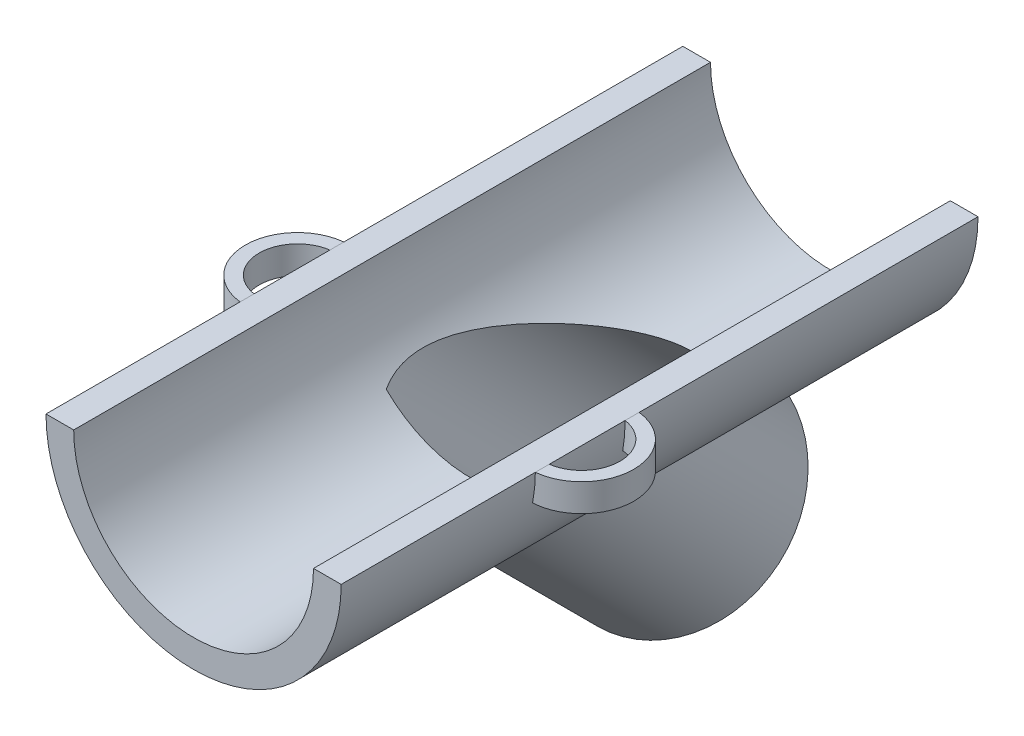
SolidWorks part; units mm, degrees
ref_plane "Front Plane" through (0, 0, 0) normal (0, 0, 1) x (1, 0, 0)
ref_plane "Top Plane" through (0, 0, 0) normal (0, 1, 0) x (1, 0, 0)
ref_plane "Right Plane" through (0, 0, 0) normal (1, 0, 0) x (0, 0, -1)
sketch "Sketch2" plane through (0, 0, 0) normal (0, 0, 1) x (1, 0, 0)
  line L0 (13.54, 0) -> (11, 0)
  line L1 (-11, 0) -> (-13.54, 0)
  arc A0 (-11, 0) -> (11, 0) centre (0, 0) ccw
  arc A1 (-13.54, 0) -> (13.54, 0) centre (0, 0) ccw
  dimension "D1" = 22
  dimension "D2" = 2.54
extrude "Boss-Extrude1" add sketch "Sketch2" along normal blind 76.2
ref_plane "Plane1" through (0, 0, 0) normal (0, 0.7071, 0.7071) x (-1, 0, 0)
sketch "Sketch4" plane through (0, 0, 0) normal (0, 0.7071, 0.7071) x (-1, 0, 0)
  line L5 (-13.54, 0) -> (-11, 0) construction
  line L10 (0, 68.58) -> (0, 0) construction
  circle A0 centre (0, 55.88) radius 10
  point P10 (0, 0)
  dimension "D4" = 20
  dimension "D5" = 55.88
extrude "Boss-Extrude4" add sketch "Sketch4" along normal up to surface (46.7315 mm away) up to face at (0, -6.77, 38.1)
sketch "Sketch9" plane through (0, 0, 0) normal (0, -0.7071, -0.7071) x (-1, 0, 0)
  circle A0 centre (0, -55.88) radius 8.5
  circle A1 centre (0, -55.88) radius 10 construction
  dimension "D1" = 17
extrude "Cut-Extrude4" cut sketch "Sketch9" against normal through all and the other way through all
sketch "Sketch10" plane through (0, 0, 0) normal (0, 0, -1) x (-1, 0, 0)
  line L0 (13.54, 0) -> (11, 0)
  line L1 (11, 0) -> (13.54, 0) construction
  line L2 (-13.54, 0) -> (-11, 0) construction
  line L3 (-11, 0) -> (-13.54, 0)
  arc A0 (-13.54, 0) -> (13.54, 0) centre (0, 0) ccw construction
  arc A1 (11, 0) -> (-11, 0) centre (0, 0) cw
  arc A2 (-11, 0) -> (11, 0) centre (0, 0) ccw construction
  arc A3 (13.54, 0) -> (-13.54, 0) centre (0, 0) cw
extrude "Cut-Extrude5" cut sketch "Sketch10" against normal blind 43.18
sketch "Sketch11" plane through (0, 0, 76.2) normal (0, 0, 1) x (1, 0, 0)
  line L0 (-11, 0) -> (-13.54, 0) construction
  line L1 (13.54, 0) -> (11, 0) construction
  line L2 (13.54, 0) -> (11, 0)
  line L3 (-11, 0) -> (-13.54, 0)
  arc A0 (11, 0) -> (-11, 0) centre (0, 0) cw
  arc A1 (13.54, 0) -> (-13.54, 0) centre (0, 0) cw
  arc A2 (-13.54, 0) -> (-8.3124, -10.6881) centre (0, 0) ccw construction
extrude "Boss-Extrude5" add sketch "Sketch11" along normal blind 25.4
sketch "Sketch12" plane through (0, 0, 0) normal (0, 1, 0) x (1, 0, 0)
  line L0 (-13.032, -83.82) -> (-13.032, -82.55)
  line L1 (13.032, -74.246) -> (13.032, -75.516)
  line L2 (13.032, -82.55) -> (13.032, -83.82)
  line L3 (13.54, -101.6) -> (13.54, -43.18) construction
  line L4 (13.54, -101.6) -> (11, -101.6) construction
  line L5 (-13.032, -74.246) -> (-13.032, -75.516)
  line L6 (-13.54, -101.6) -> (-13.54, -43.18) construction
  arc A0 (13.032, -74.246) -> (13.032, -83.82) centre (13.032, -79.033) cw
  arc A1 (13.032, -75.516) -> (13.032, -82.55) centre (13.032, -79.033) cw
  arc A2 (-13.032, -82.55) -> (-13.032, -75.516) centre (-13.032, -79.033) cw
  arc A3 (-13.032, -83.82) -> (-13.032, -74.246) centre (-13.032, -79.033) cw
  dimension "D3" = 1.27
  dimension "D1" = 0.508
  dimension "D2" = 17.78
  dimension "D4" = 0.508
extrude "Boss-Extrude6" add sketch "Sketch12" against normal blind 2.54 separate body
sketch "Sketch14" plane through (0, 0, 0) normal (0, -0.7071, -0.7071) x (1, 0, 0)
  circle A0 centre (0, 55.88) radius 10
extrude "Cut-Extrude6" cut sketch "Sketch14" against normal blind 25.4
